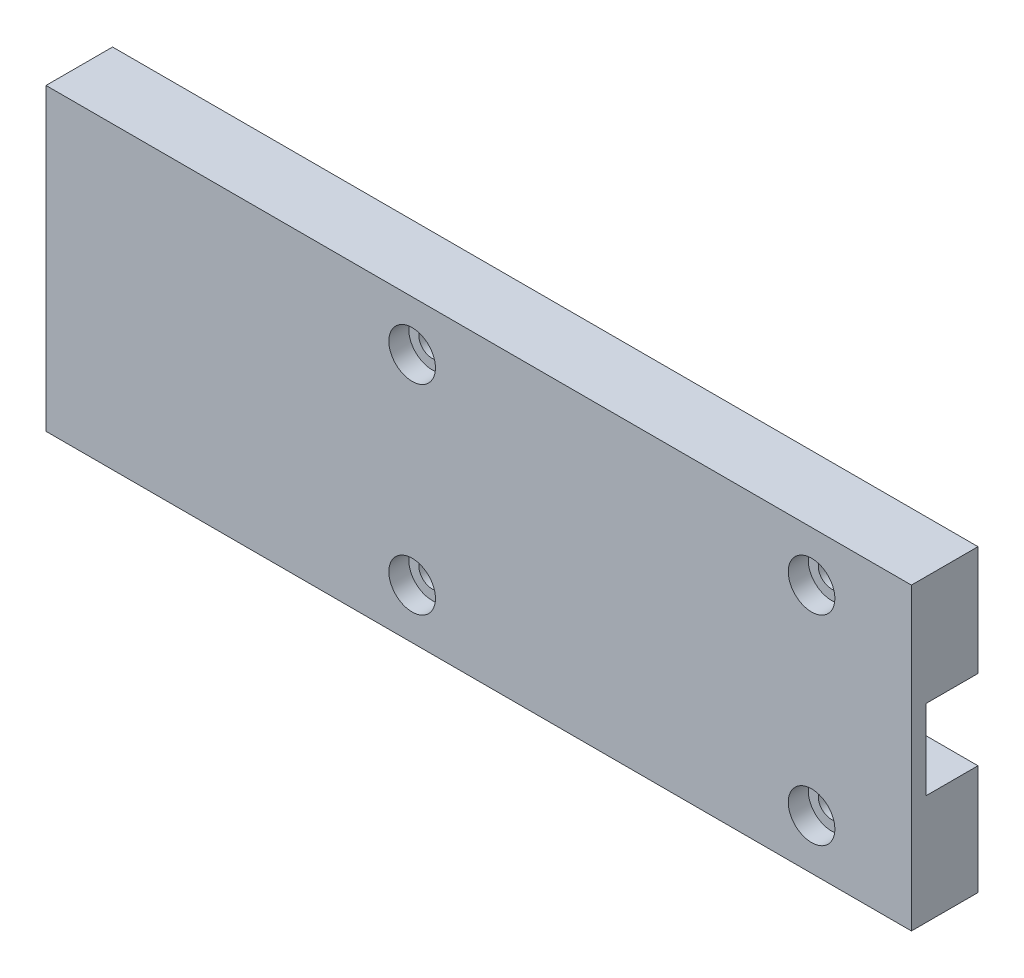
SolidWorks part; units mm, degrees
ref_plane "Front Plane" through (0, 0, 0) normal (0, 0, 1) x (1, 0, 0)
ref_plane "Top Plane" through (0, 0, 0) normal (0, 1, 0) x (1, 0, 0)
ref_plane "Right Plane" through (0, 0, 0) normal (1, 0, 0) x (0, 0, -1)
sketch "Sketch1" plane through (0, 0, 0) normal (0, 0, 1) x (1, 0, 0)
  line L0 (130, 45) -> (130, 0) construction
  line L1 (0, 0) -> (130, 0)
  line L2 (0, 0) -> (0, 45)
  line L3 (0, 45) -> (130, 45)
  line L4 (130, 0) -> (130, 45)
  line L5 (0, 0) -> (130, 45) construction
  line L6 (0, 45) -> (130, 0) construction
  line L7 (0, 45) -> (130, 45) construction
  point P4 (65, 22.5)
extrude "Boss-Extrude1" add sketch "Sketch1" along normal blind 10
sketch "Sketch2" plane through (0, 0, 0) normal (0, 0, -1) x (-1, 0, 0)
  line L0 (-130, 0) -> (-130, 45) construction
  line L1 (-130, 16.5) -> (-20, 16.5)
  line L2 (-130, 16.5) -> (-130, 28.5)
  line L3 (-130, 28.5) -> (-20, 28.5)
  line L4 (-20, 16.5) -> (-20, 28.5)
  line L5 (-130, 16.5) -> (-20, 28.5) construction
  line L6 (-130, 28.5) -> (-20, 16.5) construction
  line L7 (-130, 45) -> (0, 45) construction
  line L8 (0, 0) -> (-130, 0) construction
  point P4 (-75, 22.5)
  dimension "D1" = 16.5
  dimension "D2" = 16.5
  dimension "D3" = 110
extrude "Cut-Extrude1" cut sketch "Sketch2" against normal blind 7.8
sketch "Sketch4" plane through (0, 0, 10) normal (0, 0, 1) x (1, 0, 0)
  line L0 (130, 0) -> (130, 45) construction
  line L1 (115, 7.5) -> (55, 7.5) construction
  line L2 (115, 7.5) -> (115, 37.5) construction
  line L3 (115, 37.5) -> (55, 37.5) construction
  line L4 (55, 7.5) -> (55, 37.5) construction
  line L5 (115, 7.5) -> (55, 37.5) construction
  line L6 (115, 37.5) -> (55, 7.5) construction
  line L7 (130, 22.5) -> (0, 22.5) construction
  line L8 (0, 45) -> (0, 0) construction
  circle A0 centre (55, 37.5) radius 2
  circle A1 centre (115, 37.5) radius 2
  circle A2 centre (115, 7.5) radius 2
  circle A3 centre (55, 7.5) radius 2
  point P0 (85, 22.5)
  dimension "D4" = 4
  dimension "D1" = 30
  dimension "D2" = 60
  dimension "D3" = 15
extrude "Cut-Extrude3" cut sketch "Sketch4" against normal through all
sketch "Sketch5" plane through (0, 0, 10) normal (0, 0, 1) x (1, 0, 0)
  circle A0 centre (55, 37.5) radius 3.5
  circle A1 centre (115, 37.5) radius 3.5
  circle A2 centre (115, 7.5) radius 3.5
  circle A3 centre (55, 7.5) radius 3.5
  dimension "D1" = 7
extrude "Cut-Extrude4" cut sketch "Sketch5" against normal blind 3
sketch "Sketch6" plane through (0, 0, 0) normal (0, 0, -1) x (-1, 0, 0)
  line L1 (-4.5, 43) -> (-45.5, 43)
  line L2 (-4.5, 43) -> (-4.5, 2)
  line L3 (-4.5, 2) -> (-45.5, 2)
  line L4 (-45.5, 43) -> (-45.5, 2)
  line L5 (-4.5, 43) -> (-45.5, 2) construction
  line L6 (-4.5, 2) -> (-45.5, 43) construction
  point P4 (-25, 22.5)
extrude "Cut-Extrude5" cut sketch "Sketch6" against normal up to surface (7.8 mm away) up to face at (75, 22.5, 7.8)
